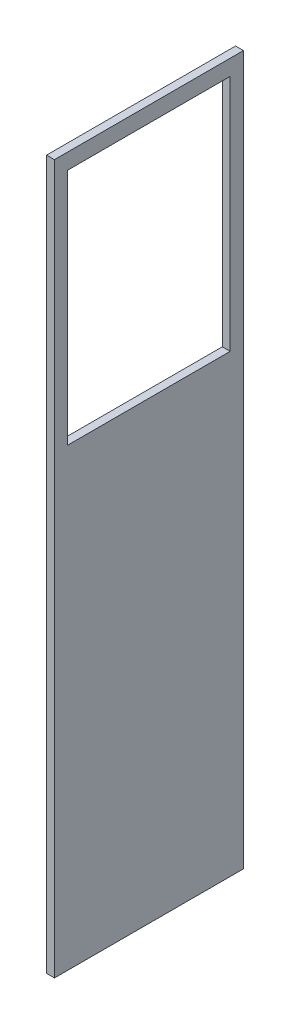
SolidWorks part; units mm, degrees
ref_plane "Front Plane" through (0, 0, 0) normal (0, 0, 1) x (1, 0, 0)
ref_plane "Top Plane" through (0, 0, 0) normal (0, 1, 0) x (1, 0, 0)
ref_plane "Right Plane" through (0, 0, 0) normal (1, 0, 0) x (0, 0, -1)
sketch "Sketch1" plane through (0, 0, 0) normal (1, 0, 0) x (0, 0, -1)
  line L1 (0, 0) -> (76.2, 0)
  line L2 (0, 0) -> (0, 285.75)
  line L3 (0, 285.75) -> (76.2, 285.75)
  line L4 (76.2, 0) -> (76.2, 285.75)
  dimension "D1" = 76.2
  dimension "D2" = 285.75
extrude "Boss-Extrude1" add sketch "Sketch1" along normal blind 3.175
ref_plane "Plane1" through (0, 0, -38.1) normal (0, 0, -1) x (-1, 0, 0)
sketch "Sketch2" plane through (0, 0, 0) normal (-1, 0, 0) x (0, 0, 1)
  line L1 (-70.866, 183.388) -> (-5.334, 183.388)
  line L2 (-70.866, 183.388) -> (-70.866, 279.4)
  line L3 (-70.866, 279.4) -> (-5.334, 279.4)
  line L4 (-5.334, 183.388) -> (-5.334, 279.4)
  line L6 (-76.2, 285.75) -> (0, 285.75) construction
  point P6 (-38.1, 285.75)
  point P7 (-38.1, 279.4)
  dimension "D1" = 96.012
  dimension "D2" = 65.532
  dimension "D3" = 6.35
extrude "Cut-Extrude1" cut sketch "Sketch2" against normal up to next
